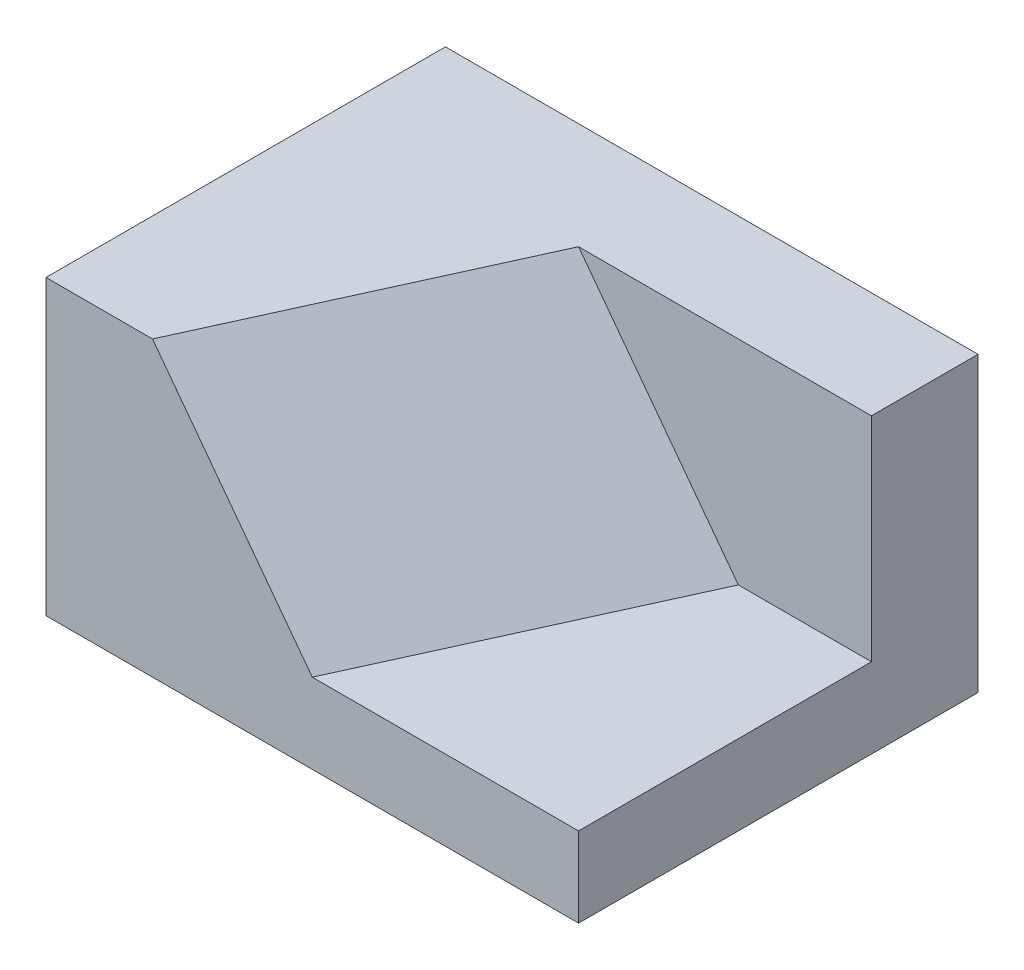
SolidWorks part; units mm, degrees
ref_plane "Front Plane" through (0, 0, 0) normal (0, 0, 1) x (1, 0, 0)
ref_plane "Top Plane" through (0, 0, 0) normal (0, 1, 0) x (1, 0, 0)
ref_plane "Right Plane" through (0, 0, 0) normal (1, 0, 0) x (0, 0, -1)
sketch "Sketch1" plane through (0, 0, 0) normal (1, 0, 0) x (0, 0, -1)
  line L0 (0, 40) -> (0, 0)
  line L1 (-55, 40) -> (20, 40)
  line L2 (-55, 40) -> (-55, -15)
  line L3 (-55, -15) -> (20, -15)
  line L4 (20, 40) -> (20, -15)
  line L5 (0, 0) -> (-55, 0)
  point P7 (0, 0)
  dimension "D1" = 75
  dimension "D2" = 55
  dimension "D3" = 20
  dimension "D4" = 15
extrude "Boss-Extrude1" add sketch "Sketch1" along normal blind 100 contours L0 L5 L2 L3 L4 L1 region at (0, 39.0699, -10)
extrude "Boss-Extrude2" add sketch "Sketch1<3>" along normal blind 75 contours L5 L0 L1 L2 region at (0, 20, 27.5)
sketch "Sketch1<3>" plane through (0, 0, 0) normal (1, 0, 0) x (0, 0, -1) same geometry as "Sketch1"
sketch "Sketch2" plane through (0, 40, 0) normal (0, 1, 0) x (1, 0, 0)
  line L0 (75, -55) -> (0, -55) construction
  line L1 (0, -55) -> (0, 20) construction
  point P0 (45, 0)
  point P1 (20, -55)
  point P6 (45, 0)
  point P7 (0, 0)
  point P9 (0, 0)
  dimension "D1" = 45
  dimension "D2" = 20
sketch "Sketch3" plane through (0, 0, 55) normal (0, 0, 1) x (1, 0, 0)
  point P0 (50, 0)
  point P1 (0, 0)
  dimension "D1" = 50
ref_plane "Plane1" through (42.3942, 31.7956, 19.2701) normal (-0.7518, -0.5639, -0.3417) x (-0.2734, -0.205, 0.9398)
sketch "Sketch4" plane through (42.3942, 31.7956, 19.2701) normal (-0.7518, -0.5639, -0.3417) x (-0.2734, -0.205, 0.9398)
  line L0 (38.0189, 20) -> (-20.5046, 5)
  line L1 (-20.5046, 5) -> (-20.5046, -45)
  line L2 (-20.5046, -45) -> (38.0189, -30)
  line L3 (38.0189, -30) -> (38.0189, 20)
extrude "Cut-Extrude1" cut sketch "Sketch4" along direction (-1, 0, 0) on the side against the normal blind 75
